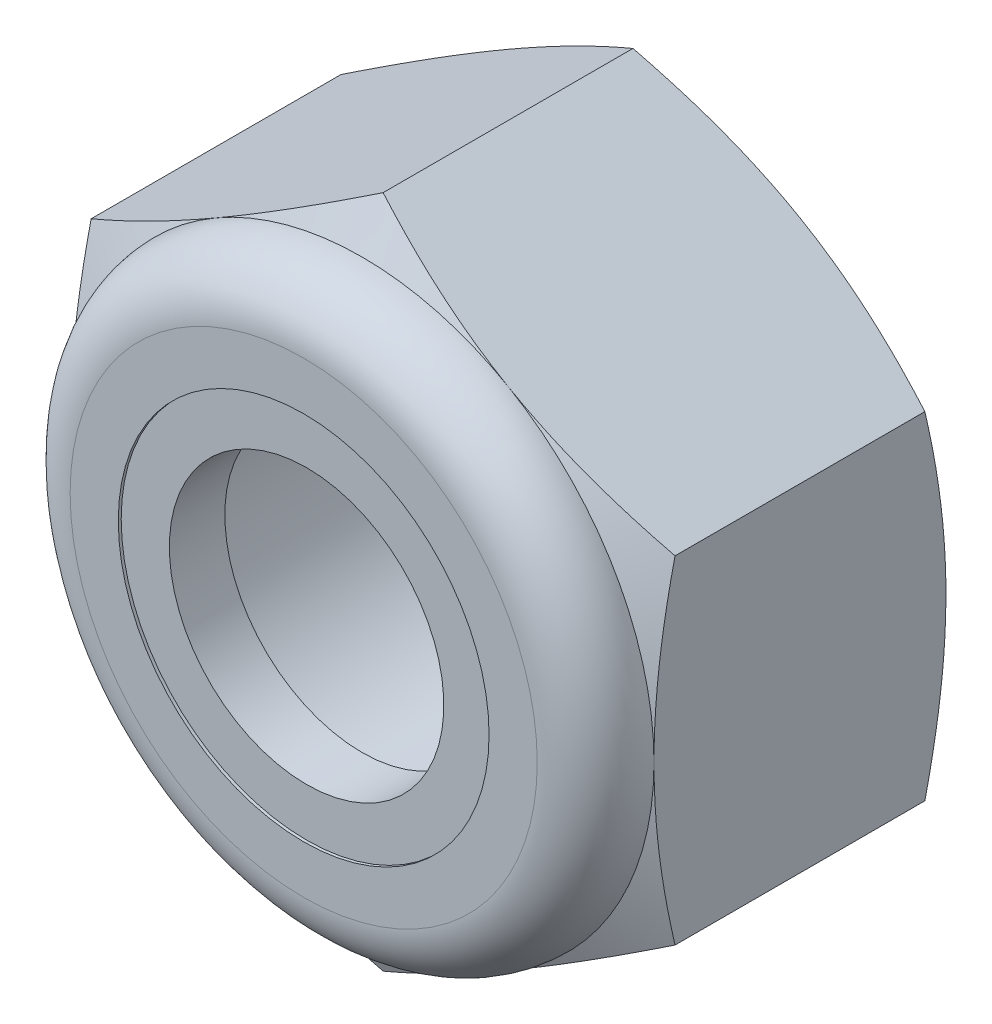
SolidWorks part; units mm, degrees
ref_plane "Front Plane" through (0, 0, 0) normal (0, 0, 1) x (1, 0, 0)
ref_plane "Top Plane" through (0, 0, 0) normal (0, 1, 0) x (1, 0, 0)
ref_plane "Right Plane" through (0, 0, 0) normal (1, 0, 0) x (0, 0, -1)
sketch "Sketch1" plane through (0, 0, 0) normal (0, 0, 1) x (1, 0, 0)
  line L1 (0, 5.7735) -> (-5, 2.8868)
  line L2 (-5, 2.8868) -> (-5, -2.8868)
  line L3 (-5, -2.8868) -> (0, -5.7735)
  line L4 (0, -5.7735) -> (5, -2.8868)
  line L5 (5, -2.8868) -> (5, 2.8868)
  line L6 (5, 2.8868) -> (0, 5.7735)
  circle A0 centre (0, 0) radius 5 construction
  circle A1 centre (0, 0) radius 3
  point P10 (0, -3)
  point P11 (0, 3)
  point P12 (0, 5)
  dimension "Thread Size" = 6
  dimension "Width" = 10
sketch "Sketch2" plane through (0, 0, 0) normal (1, 0, 0) x (0, 0, -1)
  line L0 (3, 0) -> (-3, 0) construction
  line L1 (-3, 3) -> (3, 3) construction
  line L2 (-2.95, -3.1752) -> (-4.27, -3.1752) construction
  line L3 (-3.9375, 3.1083) -> (-2.9375, 3.1083) construction
  line L4 (-2.9375, 3.1083) -> (-3.4375, 2.2422) construction
  line L5 (-3.4375, 2.2422) -> (-3.9375, 3.1083) construction
  line L6 (-3.875, 3) -> (-3, 3) construction
  line L7 (-3.5, 2.3505) -> (-3.375, 2.3505) construction
  line L8 (-3.4375, 2.3505) -> (-3.4375, 2.2422) construction
  line L9 (-3.4375, 3) -> (-3.4375, 3.1083) construction
  line L10 (-2.9688, 3.0541) -> (-3.9063, 3.0541)
  line L11 (-3.9063, 3.0541) -> (-3.5, 2.3505)
  line L12 (-3.5, 2.3505) -> (-3.375, 2.3505)
  line L13 (-3.375, 2.3505) -> (-2.9688, 3.0541)
  line L14 (3, 0) -> (4.27, 0)
  line L15 (4.27, 0) -> (4.27, 7.0435)
  line L16 (0, 7.0435) -> (0, 5.7735) construction
  line L17 (0, 5.7735) -> (0, 2.8868) construction
  line L18 (3, 5) -> (-2, 5) construction
  line L19 (-3.5, -2.3505) -> (-3.375, -2.3505) construction
  line L20 (3, 5) -> (3, 0)
  line L21 (2.6393, 5.7735) -> (-1.6393, 5.7735)
  line L22 (3, 5) -> (2.6393, 5.7735)
  line L23 (-3, 0) -> (-3, 4) construction
  line L24 (-2, 5) -> (-1.6393, 5.7735)
  line L25 (4.27, 7.0435) -> (-4.27, 7.0435)
  line L26 (-3, 4) -> (-4.27, 4)
  line L27 (-4.27, 4) -> (-4.27, 7.0435)
  line L28 (-2.95, 4) -> (-2.95, 2.3505) construction
  line L29 (-2.95, 3.1752) -> (-4.27, 3.1752)
  line L30 (-4.27, 3.1752) -> (-4.27, 0)
  line L31 (-4.27, 0) -> (-2, 0)
  line L32 (-2, 0) -> (-2, 4.95)
  line L33 (-2.95, 3.1752) -> (-2.95, 4)
  arc A0 (-2, 5) -> (-3, 4) centre (-2, 4) ccw
  arc A1 (-2, 4.95) -> (-2.95, 4) centre (-2, 4) ccw
  point P4 (0, 0)
  point P18 (-3.4375, 3.0541)
  point P22 (-3.4375, 3.0541)
  point P33 (0, 5.7735)
  point P48 (-4.27, -3.1752)
  point P51 (-3.5, -2.3505)
  dimension "Height" = 6
  dimension "Pitch" = 1
  dimension "D1" = 0.125
  dimension "D2" = 1.27
  dimension "D3" = 25
  dimension "D4" = 1
  dimension "D5" = 25
  dimension "D6" = 0.05
sketch "Sketch3" plane through (0, 0, 0) normal (0, 0, 1) x (1, 0, 0)
  line L0 (0, -5.7735) -> (5, -2.8868) construction
  line L1 (5, -2.8868) -> (5, 2.8868) construction
  line L2 (5, 2.8868) -> (0, 5.7735) construction
  line L3 (0, 5.7735) -> (-5, 2.8868) construction
  line L4 (-5, 2.8868) -> (-5, -2.8868) construction
  line L5 (-5, -2.8868) -> (0, -5.7735) construction
  line L6 (0, -5.7735) -> (5, -2.8868)
  line L7 (5, -2.8868) -> (5, 2.8868)
  line L8 (5, 2.8868) -> (0, 5.7735)
  line L9 (0, 5.7735) -> (-5, 2.8868)
  line L10 (-5, 2.8868) -> (-5, -2.8868)
  line L11 (-5, -2.8868) -> (0, -5.7735)
  circle A0 centre (0, 0) radius 3 construction
  circle A1 centre (0, 0) radius 3
extrude "Boss-Extrude1" add sketch "Sketch3" along normal mid plane 6
sketch "Sketch4" plane through (0, 0, 0) normal (1, 0, 0) x (0, 0, -1)
  line L0 (4.27, 7.0435) -> (-4.27, 7.0435) construction
  line L1 (-4.27, 4) -> (-4.27, 7.0435) construction
  line L2 (-3, 4) -> (-4.27, 4) construction
  line L3 (-2, 5) -> (-1.6393, 5.7735) construction
  line L4 (2.6393, 5.7735) -> (-1.6393, 5.7735) construction
  line L5 (3, 5) -> (2.6393, 5.7735) construction
  line L6 (3, 5) -> (3, 0) construction
  line L7 (3, 0) -> (4.27, 0) construction
  line L8 (4.27, 0) -> (4.27, 7.0435) construction
  line L9 (-4.27, 3.1752) -> (-4.27, 0) construction
  line L10 (-4.27, 0) -> (-2, 0) construction
  line L11 (-2, 0) -> (-2, 4.95) construction
  line L12 (-2.95, 3.1752) -> (-2.95, 4) construction
  line L13 (-2.95, 3.1752) -> (-4.27, 3.1752) construction
  line L14 (4.27, 7.0435) -> (-4.27, 7.0435)
  line L15 (-4.27, 4) -> (-4.27, 7.0435)
  line L16 (-3, 4) -> (-4.27, 4)
  line L17 (-2, 5) -> (-1.6393, 5.7735)
  line L18 (2.6393, 5.7735) -> (-1.6393, 5.7735)
  line L19 (3, 5) -> (2.6393, 5.7735)
  line L20 (3, 5) -> (3, 0)
  line L21 (3, 0) -> (4.27, 0)
  line L22 (4.27, 0) -> (4.27, 7.0435)
  line L23 (-4.27, 3.1752) -> (-4.27, 0)
  line L24 (-4.27, 0) -> (-2, 0)
  line L25 (-2, 0) -> (-2, 4.95)
  line L26 (-2.95, 3.1752) -> (-2.95, 4)
  line L27 (-2.95, 3.1752) -> (-4.27, 3.1752)
  arc A0 (-2, 5) -> (-3, 4) centre (-2, 4) ccw construction
  arc A1 (-2, 4.95) -> (-2.95, 4) centre (-2, 4) ccw construction
  arc A2 (-2, 5) -> (-3, 4) centre (-2, 4) ccw
  arc A3 (-2, 4.95) -> (-2.95, 4) centre (-2, 4) ccw
revolve "Cut-Revolve1" cut sketch "Sketch4" angle 360 about L0
sketch "Sketch5" plane through (0, 0, 0) normal (1, 0, 0) x (0, 0, -1)
  line L0 (-2.95, 4) -> (-2.95, 2.3505) construction
  line L1 (-2, 0) -> (-2, 4.95) construction
  line L2 (-2.95, 4) -> (-2.95, 2.3505)
  line L3 (-2, 2.3505) -> (-2, 4.95)
  line L4 (-2.95, 2.3505) -> (-2, 2.3505)
  arc A0 (-2, 4.95) -> (-2.95, 4) centre (-2, 4) ccw construction
  arc A1 (-2, 4.95) -> (-2.95, 4) centre (-2, 4) ccw
revolve "Revolve1" add sketch "Sketch5" angle 360 about L0
sketch "Sketch6" [suppressed] plane through (0, 0, 3) normal (0, 0, 1) x (1, 0, 0)
  circle A0 centre (0, 0) radius 3 construction
  circle A1 centre (0, 0) radius 3
curve "Helix/Spiral1" [suppressed] pitch 1 height 7 turns 7
sketch "Sketch7" [suppressed] plane through (0, 0, 0) normal (1, 0, 0) x (0, 0, -1)
  line L0 (-3.9063, 3.0541) -> (-3.5, 2.3505) construction
  line L1 (-3.5, 2.3505) -> (-3.375, 2.3505) construction
  line L2 (-3.375, 2.3505) -> (-2.9688, 3.0541) construction
  line L3 (-2.9688, 3.0541) -> (-3.9063, 3.0541) construction
  line L4 (-3.9063, 3.0541) -> (-3.5, 2.3505)
  line L5 (-3.5, 2.3505) -> (-3.375, 2.3505)
  line L6 (-3.375, 2.3505) -> (-2.9688, 3.0541)
  line L7 (-2.9688, 3.0541) -> (-3.9063, 3.0541)
sweep "Sweep1" [suppressed] add profiles "Sketch7" path "Helix/Spiral1"
sketch "Sketch8" [suppressed] plane through (0, 0, -3) normal (0, 0, -1) x (-1, 0, 0)
  circle A2 centre (0, 0) radius 3.0541
  point P2 (0, 3.0541)
extrude "Cut-Extrude1" [suppressed] cut sketch "Sketch8" along normal through all and the other way through all draft 60
sketch "Sketch9" [suppressed] plane through (0, 0, 2) normal (0, 0, 1) x (1, 0, 0)
  circle A2 centre (0, 0) radius 3.0541
  circle A3 centre (0, 0) radius 2.3505 construction
  point P2 (0, 3.0541)
  point P4 (0, 2.3505)
extrude "Cut-Extrude2" [suppressed] cut sketch "Sketch9" along normal through all and the other way through all draft 60
equation "\"D1@Sketch2\" = \"Pitch@Sketch2\" / 8"
equation "\"D4@Sketch2\"=\"Height@Sketch2\"/6"
equation "\"D1@Boss-Extrude1\"=\"Height@Sketch2\""
equation "\"D3@Helix/Spiral1\"=\"Height@Sketch2\"+\"Pitch@Sketch2\""
equation "\"D4@Helix/Spiral1\"=\"Pitch@Sketch2\""
equation "\"D6@Sketch2\"=\"Pitch@Sketch2\"*0.05"
